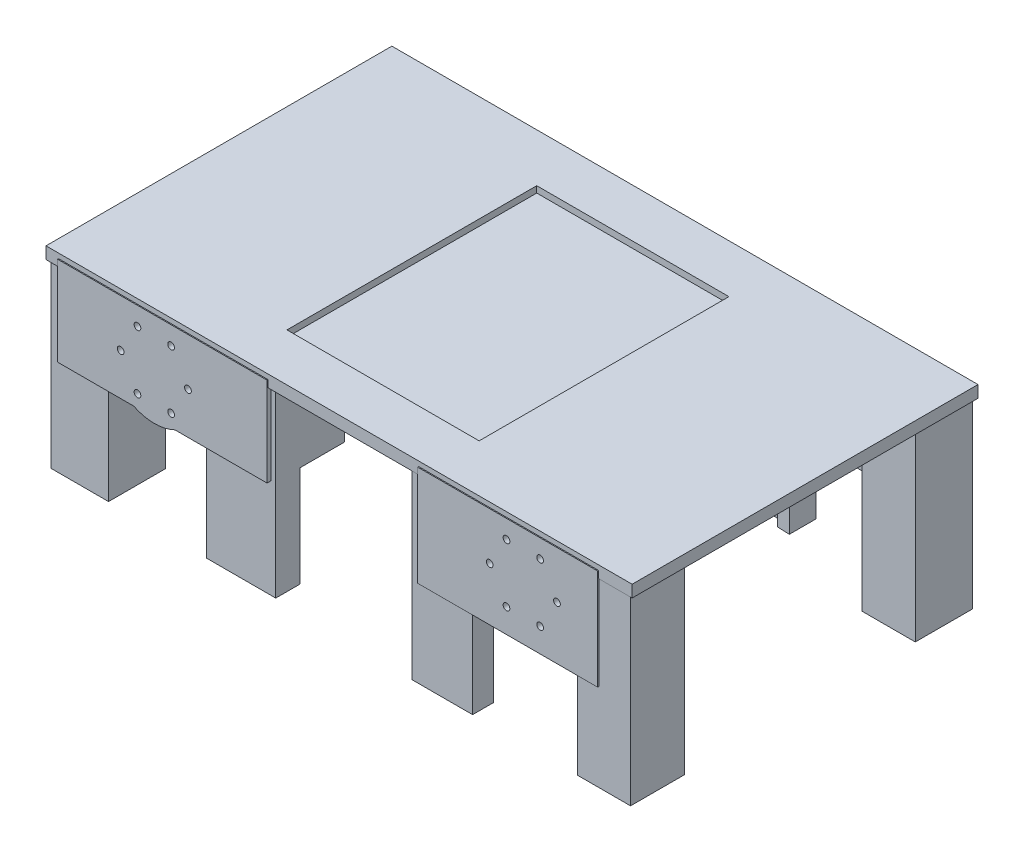
SolidWorks part; units mm, degrees
ref_plane "Front Plane" through (0, 0, 0) normal (0, 0, 1) x (1, 0, 0)
ref_plane "Top Plane" through (0, 0, 0) normal (0, 1, 0) x (1, 0, 0)
ref_plane "Right Plane" through (0, 0, 0) normal (1, 0, 0) x (0, 0, -1)
sketch "MotorHoldersSketch" plane through (0, 0, 0) normal (0, 0, 1) x (1, 0, 0)
  line L0 (0, 0) -> (170, 0) construction
  line L1 (0, 0) -> (0, 21.41) construction
  line L2 (170, 0) -> (170, 21.41) construction
  circle A0 centre (0, 0) radius 21.41
  circle A1 centre (170, 0) radius 21.41
ref_axis "MotorCenterAxis1" through (0, 0, 0) along (0, 0, 1)
ref_axis "MotorCenterAxis2" through (170, 0, 0) along (0, 0, 1)
extrude "MotorHolders" add sketch "MotorHoldersSketch" along normal blind 80 and the other way blind 80
sketch "Sketch3" plane through (0, 0, 0) normal (0, 0, 1) x (1, 0, 0)
  line L1 (1.9406, 21.133) -> (168.3435, 21.133)
  line L2 (1.9406, 21.133) -> (1.9406, 18.3155)
  line L3 (1.9406, 18.3155) -> (168.3435, 18.3155)
  line L4 (168.3435, 21.133) -> (168.3435, 18.3155)
extrude "Boss-Extrude2" add sketch "Sketch3" along normal blind 70 and the other way blind 70
sketch "Sketch4" plane through (0, 0, 0) normal (0, 1, 0) x (1, 0, 0)
  line L1 (221.2811, -76.3794) -> (-41.4939, -76.3794)
  line L2 (221.2811, -76.3794) -> (221.2811, 76.7331)
  line L3 (221.2811, 76.7331) -> (-41.4939, 76.7331)
  line L4 (-41.4939, -76.3794) -> (-41.4939, 76.7331)
extrude "Cut-Extrude1" cut sketch "Sketch4" against normal blind 23
ref_axis "Axis3" through (170, 0, 0) along (0, -1, 0)
sketch3d "ReferencePlanePosition"
  line L0 (170, 0, 0) -> (170, -34.8293, 0)
  line L1 (170, 0, 0) -> (170, -38.994, 0) construction
ref_plane "ReferencePlane" through (170, -34.8293, 0) normal (0, -1, 0) x (-1, 0, 0)
sketch "Sketch6" plane through (170, -34.8293, 0) normal (0, -1, 0) x (-1, 0, 0)
  line L1 (219.5858, 78.949) -> (193.3762, 78.949)
  line L2 (219.5858, 78.949) -> (219.5858, 52.706)
  line L3 (219.5858, 52.706) -> (193.3762, 52.706)
  line L4 (193.3762, 78.949) -> (193.3762, 52.706)
  line L5 (219.3147, -52.1095) -> (192.7905, -52.1095)
  line L6 (219.3147, -52.1095) -> (219.3147, -78.2822)
  line L7 (219.3147, -78.2822) -> (192.7905, -78.2822)
  line L8 (192.7905, -52.1095) -> (192.7905, -78.2822)
  line L9 (48.8879, 77.8627) -> (22.9134, 77.8627)
  line L10 (48.8879, 77.8627) -> (48.8879, 40.7512)
  line L11 (48.8879, 40.7512) -> (22.9134, 40.7512)
  line L12 (22.9134, 77.8627) -> (22.9134, 40.7512)
  line L13 (51.9065, -44.1716) -> (23.919, -44.1716)
  line L14 (51.9065, -44.1716) -> (51.9065, -79.4437)
  line L15 (51.9065, -79.4437) -> (23.919, -79.4437)
  line L16 (23.919, -44.1716) -> (23.919, -79.4437)
  line L17 (213.765, 71.7736) -> (201.9877, 71.7736)
  line L18 (213.765, 71.7736) -> (213.765, 60.5121)
  line L19 (213.765, 60.5121) -> (201.9877, 60.5121)
  line L20 (201.9877, 71.7736) -> (201.9877, 60.5121)
  line L21 (41.3552, 69.1777) -> (28.5109, 69.1777)
  line L22 (41.3552, 69.1777) -> (41.3552, 50.8413)
  line L23 (41.3552, 50.8413) -> (28.5109, 50.8413)
  line L24 (28.5109, 69.1777) -> (28.5109, 50.8413)
  line L25 (43.3068, -72.8101) -> (32.1723, -72.8101)
  line L26 (43.3068, -72.8101) -> (43.3068, -54.7747)
  line L27 (43.3068, -54.7747) -> (32.1723, -54.7747)
  line L28 (32.1723, -72.8101) -> (32.1723, -54.7747)
  line L29 (211.9411, -70.4881) -> (201.0982, -70.4881)
  line L30 (211.9411, -70.4881) -> (211.9411, -60.1404)
  line L31 (211.9411, -60.1404) -> (201.0982, -60.1404)
  line L32 (201.0982, -70.4881) -> (201.0982, -60.1404)
  line L33 (147.5893, 44.665) -> (120.8298, 44.665)
  line L34 (147.5893, 44.665) -> (147.5893, 78.949)
  line L35 (147.5893, 78.949) -> (120.8298, 78.949)
  line L36 (120.8298, 44.665) -> (120.8298, 78.949)
  line L37 (140.53, 55.3301) -> (128.1225, 55.3301)
  line L38 (140.53, 55.3301) -> (140.53, 71.7736)
  line L39 (140.53, 71.7736) -> (128.1225, 71.7736)
  line L40 (128.1225, 55.3301) -> (128.1225, 71.7736)
  line L41 (147.5893, -78.2822) -> (115.7712, -78.2822)
  line L42 (147.5893, -78.2822) -> (147.5893, -46.6486)
  line L43 (147.5893, -46.6486) -> (115.7712, -46.6486)
  line L44 (115.7712, -78.2822) -> (115.7712, -46.6486)
  line L45 (140.53, -70.4881) -> (123.9926, -70.4881)
  line L46 (140.53, -70.4881) -> (140.53, -56.0516)
  line L47 (140.53, -56.0516) -> (123.9926, -56.0516)
  line L48 (123.9926, -70.4881) -> (123.9926, -56.0516)
  line L49 (-24.4408, -79.4437) -> (-48.8506, -79.4437)
  line L50 (-24.4408, -79.4437) -> (-24.4408, -54.5097)
  line L51 (-24.4408, -54.5097) -> (-48.8506, -54.5097)
  line L52 (-48.8506, -79.4437) -> (-48.8506, -54.5097)
  line L53 (-24.4408, 77.8627) -> (-49.0581, 77.8627)
  line L54 (-24.4408, 77.8627) -> (-24.4408, 51.5325)
  line L55 (-24.4408, 51.5325) -> (-49.0581, 51.5325)
  line L56 (-49.0581, 77.8627) -> (-49.0581, 51.5325)
  line L57 (-41.8141, -72.8101) -> (-31.6362, -72.8101)
  line L58 (-41.8141, -72.8101) -> (-41.8141, -62.9794)
  line L59 (-41.8141, -62.9794) -> (-31.6362, -62.9794)
  line L60 (-31.6362, -72.8101) -> (-31.6362, -62.9794)
  line L61 (-31.6362, 69.1777) -> (-41.5347, 69.1777)
  line L62 (-31.6362, 69.1777) -> (-31.6362, 58.5421)
  line L63 (-31.6362, 58.5421) -> (-41.5347, 58.5421)
  line L64 (-41.5347, 69.1777) -> (-41.5347, 58.5421)
extrude "PowerBankHolders" add sketch "Sketch6" along normal blind 30 and the other way blind 55 separate body
sketch3d "3DSketch3"
  line L0 (170, 0, 0) -> (170, -64.5, 0) construction
ref_plane "Plane2" through (170, -64.5, 0) normal (0, -1, 0) x (-1, 0, 0)
sketch "Sketch7" plane through (170, -64.5, 0) normal (0, -1, 0) x (-1, 0, 0)
  line L1 (-9.5047, -80.801) -> (181.32, -80.801)
  line L2 (-9.5047, -80.801) -> (-9.5047, 73.8662)
  line L3 (-9.5047, 73.8662) -> (181.32, 73.8662)
  line L4 (181.32, -80.801) -> (181.32, 73.8662)
  line L5 (151.8712, -54.3972) -> (26.5361, -54.3972)
  line L6 (151.8712, -54.3972) -> (151.8712, 46.2413)
  line L7 (151.8712, 46.2413) -> (26.5361, 46.2413)
  line L8 (26.5361, -54.3972) -> (26.5361, 46.2413)
ref_point "Point1"
ref_point "Point2"
sketch3d "3DSketch11"
  line L0 (0, 0, -80) -> (170, 0, 80) construction
  point P4 (85, 0, 0)
sketch "MotorHolderExtrudeSketch" plane through (0, 0, 0) normal (0, 0, 1) x (1, 0, 0)
  circle A0 centre (170, 0) radius 18.415
  circle A1 centre (0, 0) radius 18.415
  circle A3 centre (0, 0) radius 21.41 construction
  circle A4 centre (170, 0) radius 21.41 construction
ref_point "TopOfMotors"
ref_plane "TangentToTopOfMotors" through (0, -18.415, 0) normal (0, 1, 0) x (1, 0, 0)
ref_axis "Axis4" through (85, 0, 0) along (0, -1, 0)
ref_plane "BottomOfPowerBankRegion" through (0, -18.425, 0) normal (0, 1, 0) x (1, 0, 0)
sketch "Sketch11" plane through (0, -18.425, 0) normal (0, 1, 0) x (1, 0, 0)
  line L0 (-18.9327, 3.7419) -> (188.9327, -3.7419) construction
  line L5 (-18.9327, -64.7581) -> (-18.9327, 72.2419)
  line L6 (188.9327, 63.7581) -> (188.9327, -71.2419)
  line L7 (188.9327, -71.2419) -> (-18.9327, -64.7581)
  line L8 (188.9327, 63.7581) -> (-18.9327, 72.2419)
  circle A0 centre (85, 0) radius 104 construction
ref_point "CenterAtBottomOfPowerBank"
ref_plane "TopOfPowerBankPlane" through (0, -52.425, 0) normal (0, 1, 0) x (1, 0, 0)
sketch "Sketch13" plane through (0, -52.425, 0) normal (0, 1, 0) x (1, 0, 0)
  line L1 (-19.4498, 72.5454) -> (166.1636, 72.5454)
  line L2 (-19.4498, 72.5454) -> (-19.4498, -78.2051)
  line L3 (-19.4498, -78.2051) -> (166.1636, -78.2051)
  line L4 (166.1636, 72.5454) -> (166.1636, -78.2051)
  line L5 (19.3173, -49.583) -> (137.9607, -49.583)
  line L6 (19.3173, -49.583) -> (19.3173, -21.0549)
  line L7 (19.3173, -21.0549) -> (137.9607, -21.0549)
  line L8 (137.9607, -49.583) -> (137.9607, -21.0549)
  line L9 (19.3173, 56.6778) -> (137.9607, 56.6778)
  line L10 (19.3173, 56.6778) -> (19.3173, 36.3234)
  line L11 (19.3173, 36.3234) -> (137.9607, 36.3234)
  line L12 (137.9607, 56.6778) -> (137.9607, 36.3234)
  line L13 (19.3173, 18.3186) -> (137.9607, 18.3186)
  line L14 (19.3173, 18.3186) -> (19.3173, -7.3615)
  line L15 (19.3173, -7.3615) -> (137.9607, -7.3615)
  line L16 (137.9607, 18.3186) -> (137.9607, -7.3615)
sketch "Sketch15" plane through (147.0866, 0, 0) normal (1, 0, 0) x (0, 0, -1)
  line L1 (72.5313, -25.7765) -> (45.7099, -25.7765)
  line L2 (72.5313, -25.7765) -> (72.5313, -24.2242)
  line L3 (72.5313, -24.2242) -> (45.7099, -24.2242)
  line L4 (45.7099, -25.7765) -> (45.7099, -24.2242)
extrude "PowerBankExtrude" cut sketch "Sketch11" against normal blind 64
ref_plane "Plane6" through (0, 0, 0) normal (0, 0, 1) x (1, 0, 0)
sketch "Sketch16" plane through (0, 0, 0) normal (0, 0, 1) x (1, 0, 0)
  line L0 (170, 0) -> (170, -13.42)
  line L1 (170, 0) -> (170, -34.8293) construction
  line L2 (170, -13.42) -> (162.25, -13.42) construction
  line L3 (170, -13.42) -> (177.75, -13.42) construction
  line L5 (170, 0) -> (185.5, 0) construction
  line L6 (170, 0) -> (154.5, 0) construction
  line L7 (170, 0) -> (170, 13.42) construction
  line L8 (170, 0) -> (170, 21.41) construction
  line L9 (170, 13.42) -> (177.75, 13.42) construction
  line L10 (170, 13.42) -> (162.25, 13.42)
ref_axis "BoltAxisA" through (185.5, 0, 0) along (0, 0, 1)
ref_axis "BoltAxisB" through (177.75, -13.42, 0) along (0, 0, 1)
ref_axis "BoltAxisC" through (162.25, -13.42, 0) along (0, 0, 1)
ref_axis "BoltAxisD" through (154.5, 0, 0) along (0, 0, 1)
ref_axis "BoltAxisE" through (162.25, 13.42, 0) along (0, 0, 1)
ref_axis "BoltAxisF" through (177.75, 13.42, 0) along (0, 0, 1)
ref_point "Point6"
ref_point "Point7"
ref_point "Point8"
ref_point "Point9"
ref_point "Point10"
ref_point "Point11"
ref_point "Point12"
ref_point "Point13"
ref_point "Point14"
ref_point "Point15"
ref_point "Point16"
ref_point "Point17"
ref_plane "Plane7" through (0, 0, 0) normal (0, 0, 1) x (1, 0, 0)
sketch "Sketch20" plane through (0, 0, 0) normal (0, 0, 1) x (1, 0, 0)
  line L0 (0, 0) -> (0, -13.42) construction
  line L1 (0, -13.42) -> (7.75, -13.42) construction
  line L2 (0, -13.42) -> (-7.75, -13.42) construction
  line L3 (0, 0) -> (0, 13.42)
  line L5 (0, 13.42) -> (7.75, 13.42) construction
  line L6 (0, 13.42) -> (-7.75, 13.42) construction
  line L7 (0, 0) -> (15.5, 0) construction
  line L8 (0, 0) -> (-15.5, 0) construction
ref_axis "Axis11" through (15.5, 0, 0) along (0, 0, 1)
ref_axis "Axis12" through (7.75, 13.42, 0) along (0, 0, 1)
ref_axis "Axis13" through (-7.75, 13.42, 0) along (0, 0, 1)
ref_axis "Axis14" through (-15.5, 0, 0) along (0, 0, 1)
ref_axis "Axis15" through (-7.75, -13.42, 0) along (0, 0, 1)
ref_axis "Axis16" through (7.75, -13.42, 0) along (0, 0, 1)
ref_point "Point18"
ref_point "Point19"
ref_point "Point20"
ref_point "Point21"
ref_point "Point22"
ref_point "Point23"
ref_point "Point24"
ref_point "Point25"
ref_point "Point26"
ref_point "Point27"
ref_point "Point28"
ref_point "Point29"
ref_plane "BottomPlane" through (0, 21.575, 0) normal (0, 1, 0) x (1, 0, 0)
sketch "Sketch21" plane through (0, 21.575, 0) normal (0, 1, 0) x (1, 0, 0)
  line L0 (219.6842, -79.5488) -> (-50.341, -79.5488)
  line L1 (-50.341, -79.5488) -> (-50.341, 79.7899)
  line L2 (-50.341, 79.7899) -> (219.6842, 79.7899)
  line L3 (219.6842, 79.7899) -> (219.6842, -79.5488)
  line L4 (127.2472, -57.5918) -> (127.2472, 57.4773)
  line L5 (127.2472, 57.4773) -> (38.7099, 57.4773)
  line L6 (38.7099, 57.4773) -> (38.7099, -57.5918)
  line L7 (38.7099, -57.5918) -> (127.2472, -57.5918)
extrude "Boss-Extrude3" add sketch "Sketch21" along normal blind 2.5 and the other way blind 3
ref_plane "Plane8" through (0, 0, 80) normal (0, 0, 1) x (1, 0, 0)
sketch "Sketch23" plane through (0, 0, 80) normal (0, 0, 1) x (1, 0, 0)
  line L1 (51.9467, -19.2158) -> (-44.5901, -19.2158)
  line L2 (51.9467, -19.2158) -> (51.9467, 21.8402)
  line L3 (51.9467, 21.8402) -> (-44.5901, 21.8402)
  line L4 (-44.5901, -19.2158) -> (-44.5901, 21.8402)
  line L5 (121.3218, 21.8402) -> (204.258, 21.8402)
  line L6 (121.3218, 21.8402) -> (121.3218, -24.4972)
  line L7 (121.3218, -24.4972) -> (204.258, -24.4972)
  line L8 (204.258, 21.8402) -> (204.258, -24.4972)
extrude "Boss-Extrude4" add sketch "Sketch23" against normal blind 6
ref_plane "Plane9" through (0, 0, -80) normal (0, 0, -1) x (-1, 0, 0)
sketch "Sketch24" plane through (0, 0, -80) normal (0, 0, -1) x (-1, 0, 0)
  line L1 (-202.1905, -31.2913) -> (-139.5471, -31.2913)
  line L2 (-202.1905, -31.2913) -> (-202.1905, 19.2374)
  line L3 (-202.1905, 19.2374) -> (-139.5471, 19.2374)
  line L4 (-139.5471, -31.2913) -> (-139.5471, 19.2374)
  line L5 (-29.2705, -22.3716) -> (29.5505, -22.3716)
  line L6 (-29.2705, -22.3716) -> (-29.2705, 22.5226)
  line L7 (-29.2705, 22.5226) -> (29.5505, 22.5226)
  line L8 (29.5505, -22.3716) -> (29.5505, 22.5226)
extrude "Boss-Extrude5" add sketch "Sketch24" against normal blind 6
sketch "Sketch17" plane through (0, 0, 80) normal (0, 0, 1) x (1, 0, 0)
  circle A0 centre (185.5, 0) radius 1.55
  circle A1 centre (177.75, -13.42) radius 1.55
  circle A2 centre (162.25, -13.42) radius 1.55
  circle A3 centre (154.5, 0) radius 1.55
  circle A4 centre (162.25, 13.42) radius 1.55
  circle A5 centre (177.75, 13.42) radius 1.55
extrude "BoltHoles1" cut sketch "Sketch17" against normal blind 31.5
sketch "Sketch19" plane through (0, 0, -80) normal (0, 0, -1) x (-1, 0, 0)
  circle A0 centre (-185.5, 0) radius 1.55
  circle A1 centre (-177.75, -13.42) radius 1.55
  circle A2 centre (-162.25, -13.42) radius 1.55
  circle A3 centre (-154.5, 0) radius 1.55
  circle A4 centre (-162.25, 13.42) radius 1.55
  circle A5 centre (-177.75, 13.42) radius 1.55
extrude "BoltHoles2" cut sketch "Sketch19" against normal blind 31.5
sketch "BoltHolesSketch3" plane through (0, 0, 80) normal (0, 0, 1) x (1, 0, 0)
  circle A0 centre (7.75, -13.42) radius 1.55
  circle A1 centre (15.5, 0) radius 1.55
  circle A2 centre (7.75, 13.42) radius 1.55
  circle A3 centre (-7.75, 13.42) radius 1.55
  circle A4 centre (-15.5, 0) radius 1.55
  circle A5 centre (-7.75, -13.42) radius 1.55
extrude "BoltHoles3" cut sketch "BoltHolesSketch3" against normal blind 31.5
sketch "BoltHolesSketch4" plane through (0, 0, -80) normal (0, 0, -1) x (-1, 0, 0)
  circle A0 centre (-15.5, 0) radius 1.55
  circle A1 centre (-7.75, 13.42) radius 1.55
  circle A2 centre (7.75, 13.42) radius 1.55
  circle A3 centre (15.5, 0) radius 1.55
  circle A4 centre (7.75, -13.42) radius 1.55
  circle A5 centre (-7.75, -13.42) radius 1.55
extrude "BoltHoles4" cut sketch "BoltHolesSketch4" against normal blind 15
extrude "MotorHolderExtrude" cut sketch "MotorHolderExtrudeSketch" against normal blind 77 and the other way blind 77
